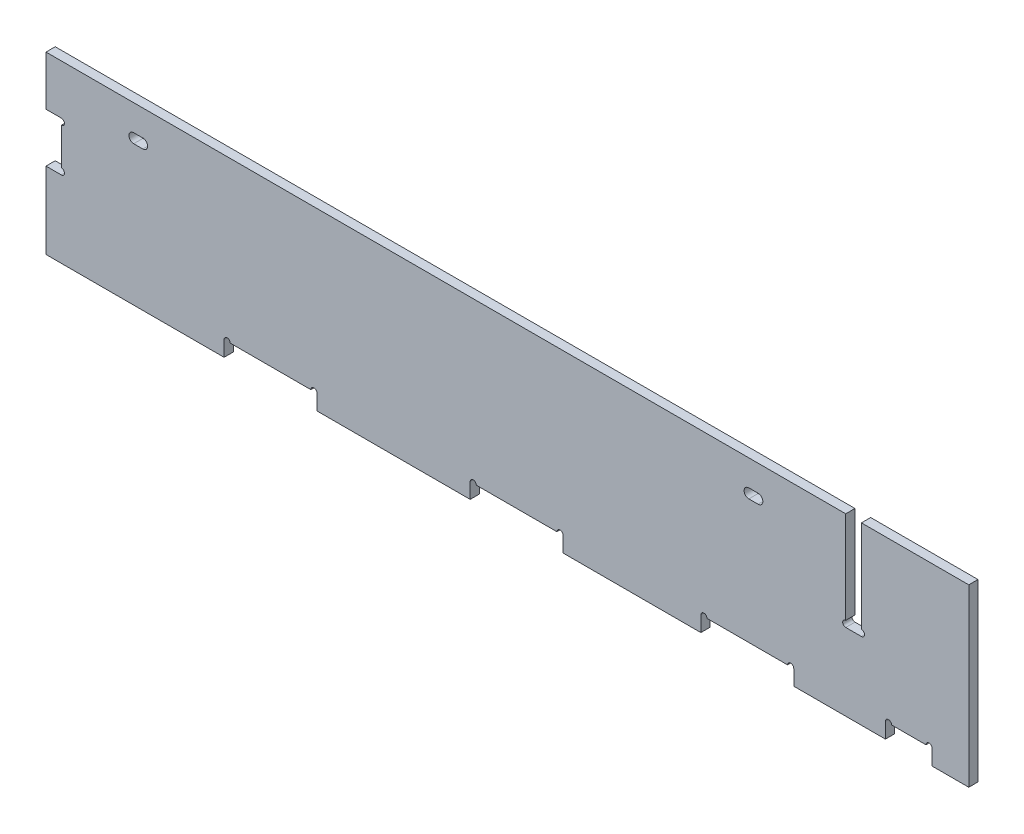
SolidWorks part; units mm, degrees
material "사용자정의 플라스틱"
ref_plane "정면" through (0, 0, 0) normal (0, 0, 1) x (1, 0, 0)
ref_plane "윗면" through (0, 0, 0) normal (0, 1, 0) x (1, 0, 0)
ref_plane "우측면" through (0, 0, 0) normal (1, 0, 0) x (0, 0, -1)
sketch "스케치1" plane through (0, 0, 0) normal (0, 0, 1) x (1, 0, 0)
  line L1 (0, 0) -> (300, 0)
  line L2 (0, 0) -> (0, 57)
  line L3 (0, 57) -> (300, 57)
  line L4 (300, 0) -> (300, 57)
  dimension "D1" = 57
  dimension "D2" = 300
extrude "보스-돌출1" add sketch "스케치1" along normal blind 3
sketch "스케치2" plane through (0, 0, 3) normal (0, 0, 1) x (1, 0, 0)
  line L1 (5, 40.9) -> (0, 40.9)
  line L2 (5, 40.9) -> (5, 24.9)
  line L3 (5, 24.9) -> (0, 24.9)
  line L4 (0, 40.9) -> (0, 24.9)
  line L7 (57.9, 5) -> (88.1, 5)
  line L8 (57.9, 5) -> (57.9, 0)
  line L9 (57.9, 0) -> (88.1, 0)
  line L10 (88.1, 5) -> (88.1, 0)
  line L13 (168.1, 0) -> (137.9, 0)
  line L14 (168.1, 0) -> (168.1, 5)
  line L15 (168.1, 5) -> (137.9, 5)
  line L16 (137.9, 0) -> (137.9, 5)
  line L18 (243.1, 0) -> (212.9, 0)
  line L19 (243.1, 0) -> (243.1, 5)
  line L20 (243.1, 5) -> (212.9, 5)
  line L21 (212.9, 0) -> (212.9, 5)
  line L23 (288.1, 0) -> (272.9, 0)
  line L24 (288.1, 0) -> (288.1, 5)
  line L25 (288.1, 5) -> (272.9, 5)
  line L26 (272.9, 0) -> (272.9, 5)
  line L27 (300, 57) -> (0, 57) construction
  line L28 (260, 57) -> (265.1, 57)
  line L29 (260, 57) -> (260, 25)
  line L30 (260, 25) -> (265.1, 25)
  line L31 (265.1, 57) -> (265.1, 25)
  line L32 (260, 26) -> (260, 57) construction
  line L33 (5, 25) -> (0, 25) construction
  line L35 (5, 40.8) -> (0, 40.8) construction
  line L36 (288, 5) -> (288, 0) construction
  line L37 (273, 5) -> (273, 0) construction
  line L38 (243, 5) -> (243, 0) construction
  line L39 (213, 5) -> (213, 0) construction
  line L40 (168, 5) -> (168, 0) construction
  line L41 (138, 5) -> (138, 0) construction
  line L42 (88, 5) -> (88, 0) construction
  line L43 (58, 5) -> (58, 0) construction
  line L44 (265, 46.85) -> (265, 15.15) construction
  dimension "D1" = 0.1
  dimension "D2" = 0.1
  dimension "D3" = 0.1
  dimension "D4" = 0.1
  dimension "D5" = 0.1
  dimension "D6" = 0.1
  dimension "D7" = 0.1
  dimension "D8" = 0.1
  dimension "D9" = 0.1
  dimension "D10" = 0.1
  dimension "D11" = 0.1
extrude "컷-돌출1" cut sketch "스케치2" against normal blind 5
sketch "스케치3" plane through (0, 0, 3) normal (0, 0, 1) x (1, 0, 0)
  line L1 (260, 25) -> (265.1, 25) construction
  line L2 (265.1, 25) -> (265.1, 57) construction
  line L3 (260, 57) -> (260, 25) construction
  line L4 (243.1, 5) -> (212.9, 5) construction
  line L5 (88.1, 5) -> (57.9, 5) construction
  line L6 (168.1, 5) -> (137.9, 5) construction
  line L7 (5, 24.9) -> (5, 40.9) construction
  line L8 (288.1, 5) -> (272.9, 5) construction
  line L9 (272.9, 5) -> (272.9, 0) construction
  line L10 (288.1, 0) -> (288.1, 5) construction
  circle A0 centre (273.9, 5) radius 1
  circle A1 centre (287.1, 5) radius 1
  circle A2 centre (260, 26) radius 1
  circle A3 centre (265.1, 26) radius 1
  circle A6 centre (213.9, 5) radius 1
  circle A7 centre (242.1, 5) radius 1
  circle A8 centre (87.1, 5) radius 1
  circle A9 centre (138.9, 5) radius 1
  circle A10 centre (167.1, 5) radius 1
  circle A11 centre (5, 25.9) radius 1
  circle A12 centre (5, 39.9) radius 1
  circle A13 centre (58.9, 5) radius 1
  dimension "D1" = 2
  dimension "D2" = 2
extrude "컷-돌출2" cut sketch "스케치3" against normal blind 5
sketch "스케치5" plane through (0, 0, 3) normal (0, 0, 1) x (1, 0, 0)
  line L0 (43.45, 57) -> (43.45, 49)
  line L1 (46.55, 45) -> (43.45, 45) construction
  line L2 (47.75, 49) -> (47.75, 46.2) construction
  line L3 (43.45, 49) -> (43.45, 46.2) construction
  line L4 (46.55, 57) -> (43.45, 57)
  line L5 (47.75, 46.2) -> (46.55, 46.2)
  line L6 (46.55, 57) -> (46.55, 49)
  line L7 (42.25, 46.2) -> (42.25, 49) construction
  line L8 (46.55, 49) -> (47.75, 49)
  line L9 (46.55, 46.2) -> (46.55, 49) construction
  line L10 (43.45, 46.2) -> (43.45, 45)
  line L11 (46.55, 49) -> (43.45, 49) construction
  line L12 (46.55, 46.2) -> (43.45, 46.2) construction
  line L13 (43.45, 46.2) -> (42.25, 46.2)
  line L14 (46.55, 46.2) -> (46.55, 45)
  line L15 (45, 45) -> (45, 43.45) construction
  line L16 (42.25, 49) -> (43.45, 49)
  line L17 (47.75, 47.6) -> (46.55, 47.6) construction
  line L18 (42.25, 47.6) -> (43.45, 47.6) construction
  line L19 (45, 46.2) -> (45, 45) construction
  line L20 (42.25, 47.6) -> (40.85, 47.6) construction
  line L21 (47.75, 47.6) -> (49.15, 47.6) construction
  line L22 (0, 57) -> (45, 57) construction
  line L23 (300, 57) -> (265.1, 57) construction
  line L24 (45, 57) -> (150, 57) construction
  line L25 (150, 57) -> (255, 57) construction
  line L26 (255, 57) -> (300, 57) construction
  line L49 (151.55, 49) -> (152.75, 49)
  line L50 (151.55, 49) -> (148.45, 49) construction
  line L51 (148.45, 46.2) -> (148.45, 45)
  line L52 (147.25, 46.2) -> (147.25, 49) construction
  line L53 (148.45, 57) -> (148.45, 49)
  line L54 (151.55, 57) -> (151.55, 49)
  line L55 (151.55, 46.2) -> (151.55, 45)
  line L56 (150, 46.2) -> (150, 45) construction
  line L57 (151.55, 46.2) -> (151.55, 49) construction
  line L58 (152.75, 47.6) -> (154.15, 47.6) construction
  line L59 (152.75, 46.2) -> (151.55, 46.2)
  line L60 (148.45, 49) -> (148.45, 46.2) construction
  line L61 (147.25, 47.6) -> (145.85, 47.6) construction
  line L62 (151.55, 57) -> (148.45, 57)
  line L63 (148.45, 46.2) -> (147.25, 46.2)
  line L64 (151.55, 46.2) -> (148.45, 46.2) construction
  line L65 (151.55, 45) -> (148.45, 45) construction
  line L66 (147.25, 47.6) -> (148.45, 47.6) construction
  line L67 (147.25, 49) -> (148.45, 49)
  line L68 (152.75, 49) -> (152.75, 46.2) construction
  line L69 (150, 45) -> (150, 43.45) construction
  line L70 (152.75, 47.6) -> (151.55, 47.6) construction
  line L71 (256.55, 49) -> (257.75, 49)
  line L72 (256.55, 49) -> (253.45, 49) construction
  line L73 (253.45, 46.2) -> (253.45, 45)
  line L74 (252.25, 46.2) -> (252.25, 49) construction
  line L75 (253.45, 57) -> (253.45, 49)
  line L76 (256.55, 57) -> (256.55, 49)
  line L77 (256.55, 46.2) -> (256.55, 45)
  line L78 (255, 46.2) -> (255, 45) construction
  line L79 (256.55, 46.2) -> (256.55, 49) construction
  line L80 (257.75, 47.6) -> (259.15, 47.6) construction
  line L81 (257.75, 46.2) -> (256.55, 46.2)
  line L82 (253.45, 49) -> (253.45, 46.2) construction
  line L83 (252.25, 47.6) -> (250.85, 47.6) construction
  line L84 (256.55, 57) -> (253.45, 57)
  line L85 (253.45, 46.2) -> (252.25, 46.2)
  line L86 (256.55, 46.2) -> (253.45, 46.2) construction
  line L87 (256.55, 45) -> (253.45, 45) construction
  line L88 (252.25, 47.6) -> (253.45, 47.6) construction
  line L89 (252.25, 49) -> (253.45, 49)
  line L90 (257.75, 49) -> (257.75, 46.2) construction
  line L91 (255, 45) -> (255, 43.45) construction
  line L92 (257.75, 47.6) -> (256.55, 47.6) construction
  arc A0 (43.45, 45) -> (46.55, 45) centre (45, 45) ccw
  arc A1 (47.75, 46.2) -> (47.75, 49) centre (47.75, 47.6) ccw
  arc A2 (42.25, 49) -> (42.25, 46.2) centre (42.25, 47.6) ccw
  arc A6 (152.75, 46.2) -> (152.75, 49) centre (152.75, 47.6) ccw
  arc A7 (147.25, 49) -> (147.25, 46.2) centre (147.25, 47.6) ccw
  arc A8 (148.45, 45) -> (151.55, 45) centre (150, 45) ccw
  arc A9 (257.75, 46.2) -> (257.75, 49) centre (257.75, 47.6) ccw
  arc A10 (252.25, 49) -> (252.25, 46.2) centre (252.25, 47.6) ccw
  arc A11 (253.45, 45) -> (256.55, 45) centre (255, 45) ccw
  dimension "D1" = 3.1
  dimension "D2" = 5.5
  dimension "D3" = 2.8
  dimension "D4" = 1.2
  dimension "D5" = 8
  dimension "D6" = 3.1
  dimension "D7" = 45
  dimension "D14" = 3.1
  dimension "D15" = 5.5
  dimension "D16" = 2.8
  dimension "D17" = 1.2
  dimension "D18" = 8
  dimension "D19" = 3.1
  dimension "D20" = 3.1
  dimension "D21" = 5.5
  dimension "D22" = 2.8
  dimension "D23" = 1.2
  dimension "D24" = 8
  dimension "D25" = 3.1
extrude "컷-돌출4" [suppressed] cut sketch "스케치5" against normal blind 10
sketch "스케치7" plane through (0, 0, 3) normal (0, 0, 1) x (1, 0, 0)
  line L0 (260, 57) -> (260, 27) construction
  line L1 (259.9, 33.9113) -> (265.2, 33.9113)
  line L2 (259.9, 33.9113) -> (259.9, 16.1106)
  line L3 (259.9, 16.1106) -> (265.2, 16.1106)
  line L4 (265.2, 33.9113) -> (265.2, 16.1106)
  line L5 (265.1, 27) -> (265.1, 57) construction
  dimension "D1" = 0.1
  dimension "D2" = 0.1
extrude "컷-돌출5" [suppressed] cut sketch "스케치7" against normal blind 10
sketch "스케치8" plane through (0, 0, 3) normal (0, 0, 1) x (1, 0, 0)
  line L0 (28.5, 47) -> (31.5, 47) construction
  line L1 (28.5, 48.55) -> (31.5, 48.55)
  line L2 (28.5, 45.45) -> (31.5, 45.45)
  line L3 (228.5, 47) -> (231.5, 47) construction
  line L4 (228.5, 48.55) -> (231.5, 48.55)
  line L5 (228.5, 45.45) -> (231.5, 45.45)
  line L6 (230, 47) -> (30, 47) construction
  line L7 (30, 47) -> (0, 47) construction
  line L8 (0, 57) -> (0, 40.9) construction
  line L9 (300, 57) -> (265.1, 57) construction
  arc A0 (28.5, 48.55) -> (28.5, 45.45) centre (28.5, 47) ccw
  arc A1 (31.5, 45.45) -> (31.5, 48.55) centre (31.5, 47) ccw
  arc A2 (228.5, 48.55) -> (228.5, 45.45) centre (228.5, 47) ccw
  arc A3 (231.5, 45.45) -> (231.5, 48.55) centre (231.5, 47) ccw
  point P2 (30, 47)
  point P7 (230, 47)
  dimension "D2" = 1.55
  dimension "D1" = 10
  dimension "D3" = 3
  dimension "D4" = 200
  dimension "D5" = 30
extrude "컷-돌출6" cut sketch "스케치8" against normal blind 10
